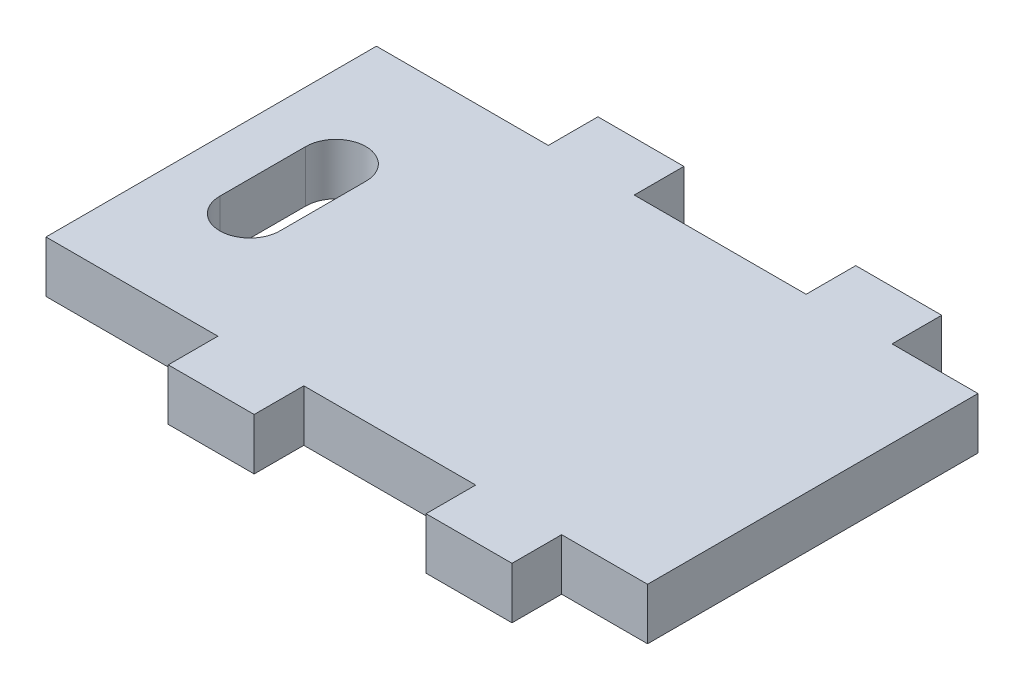
SolidWorks part; units mm, degrees
ref_plane "Front Plane" through (0, 0, 0) normal (0, 0, 1) x (1, 0, 0)
ref_plane "Top Plane" through (0, 0, 0) normal (0, 1, 0) x (1, 0, 0)
ref_plane "Right Plane" through (0, 0, 0) normal (1, 0, 0) x (0, 0, -1)
sketch "Sketch1" plane through (0, 0, 0) normal (0, 1, 0) x (1, 0, 0)
  line L0 (-25, 25) -> (-25, -25)
  line L1 (-35, 25) -> (35, 25)
  line L2 (-35, 25) -> (-35, -25)
  line L3 (-35, -25) -> (35, -25)
  line L4 (35, 25) -> (35, -25)
  line L5 (-35, 25) -> (35, -25) construction
  line L6 (-35, -25) -> (35, 25) construction
  point P0 (0, 0)
  dimension "D2" = 50
  dimension "D1" = 70
  dimension "D3" = 10
sketch "Sketch2" plane through (0, 0, 0) normal (0, 0, 1) x (1, 0, 0)
  line L0 (0, 0) -> (0, 6) construction
  line L1 (-35, 0) -> (35, 0) construction
  dimension "D1" = 6
extrude "Boss-Extrude1" add sketch "Sketch1" along normal up to vertex (6 mm away) contours L4 L1 L0 L3 region at (5, 0, 0) up to point (0, 6, 0)
sketch "Sketch3" plane through (0, 6, 0) normal (0, 1, 0) x (1, 0, 0)
  line L0 (-25, 25) -> (35, 25) construction
  line L1 (35, 25) -> (25, 25)
  line L2 (35, 25) -> (35, 19.2244)
  line L3 (35, 19.2244) -> (25, 19.2244)
  line L4 (25, 25) -> (25, 19.2244)
  line L5 (25, 19.2244) -> (15, 19.2244) construction
  line L6 (25, 19.2244) -> (25, 25) construction
  line L7 (25, 25) -> (15, 25) construction
  line L8 (15, 19.2244) -> (15, 25) construction
  line L10 (15, 25) -> (-5, 25)
  line L11 (15, 25) -> (15, 19.2244)
  line L12 (15, 19.2244) -> (-5, 19.2244)
  line L13 (-5, 25) -> (-5, 19.2244)
  line L18 (-5, 19.2244) -> (-15, 19.2244) construction
  line L19 (-5, 19.2244) -> (-5, 25) construction
  line L20 (-5, 25) -> (-15, 25) construction
  line L21 (-15, 19.2244) -> (-15, 25) construction
  line L22 (-25, 25) -> (-15, 25)
  line L23 (-25, 25) -> (-25, 19.2244)
  line L24 (-25, 19.2244) -> (-15, 19.2244)
  line L25 (-15, 25) -> (-15, 19.2244)
  dimension "D1" = 10
  dimension "D2" = 20
  dimension "D3" = 5.7756
extrude "Cut-Extrude2" cut sketch "Sketch3" against normal through all
mirror "Mirror2" about plane through (0, 0, 0) normal (0, 0, 1) of "Cut-Extrude2"
sketch "Sketch4" plane through (0, 6, 0) normal (0, 1, 0) x (1, 0, 0)
  line L1 (-25, -19.2244) -> (-35, -19.2244)
  line L2 (-25, -19.2244) -> (-25, 19.2244)
  line L3 (-25, 19.2244) -> (-35, 19.2244)
  line L4 (-35, -19.2244) -> (-35, 19.2244)
  point P5 (0, 0)
  point P8 (-35, -19)
extrude "Boss-Extrude2" add sketch "Sketch4" against normal up to surface (6 mm away) contours L3 L4 L1 L2 up to face at (5, 0, 0)
sketch "Sketch5" plane through (0, 6, 0) normal (0, 1, 0) x (1, 0, 0)
  line L0 (-25.5, -5) -> (-25.5, 5) construction
  line L1 (-29, -5) -> (-29, 5)
  line L2 (-22, -5) -> (-22, 5)
  line L3 (-25.5, 0) -> (0, 0) construction
  line L4 (-29, 0) -> (-35, 0)
  line L5 (-35, -19.2244) -> (-35, 19.2244) construction
  arc A0 (-29, -5) -> (-22, -5) centre (-25.5, -5) ccw
  arc A1 (-22, 5) -> (-29, 5) centre (-25.5, 5) ccw
  point P2 (-25.5, 0)
  dimension "D1" = 6
  dimension "D2" = 7
  dimension "D3" = 10
extrude "Cut-Extrude3" cut sketch "Sketch5" against normal through all contours L2 A1 L1 A0 region at (-25.5, 6, 0)
equation "\"glass_width\" = 150"
equation "\"glass_height\"= 100"
equation "\"glass_thickness\"= 4"
equation "\"brood_space\"= 42"
equation "\"t1\"= 6"
equation "\"t2\"= 3.2"
equation "\"box_depth\"= \"brood_space\" + \"glass_thickness\" + \"glass_thickness\" + \"t2\" + \"t2\""
equation "\"box_width\"= \"glass_width\" + \"t1\" + \"t1\""
equation "\"food_height\"= 70"
equation "\"box_height\" = \"glass_height\" + ( \"t1\" * 3 ) + \"food_height\""
equation "\"D1@Sketch2\"=\"t1\""
equation "\"D2@Sketch1\"=\"glass_thickness\"+\"glass_thickness\"+\"brood_space\""
equation "\"D1@Sketch1\"=\"food_height\""
